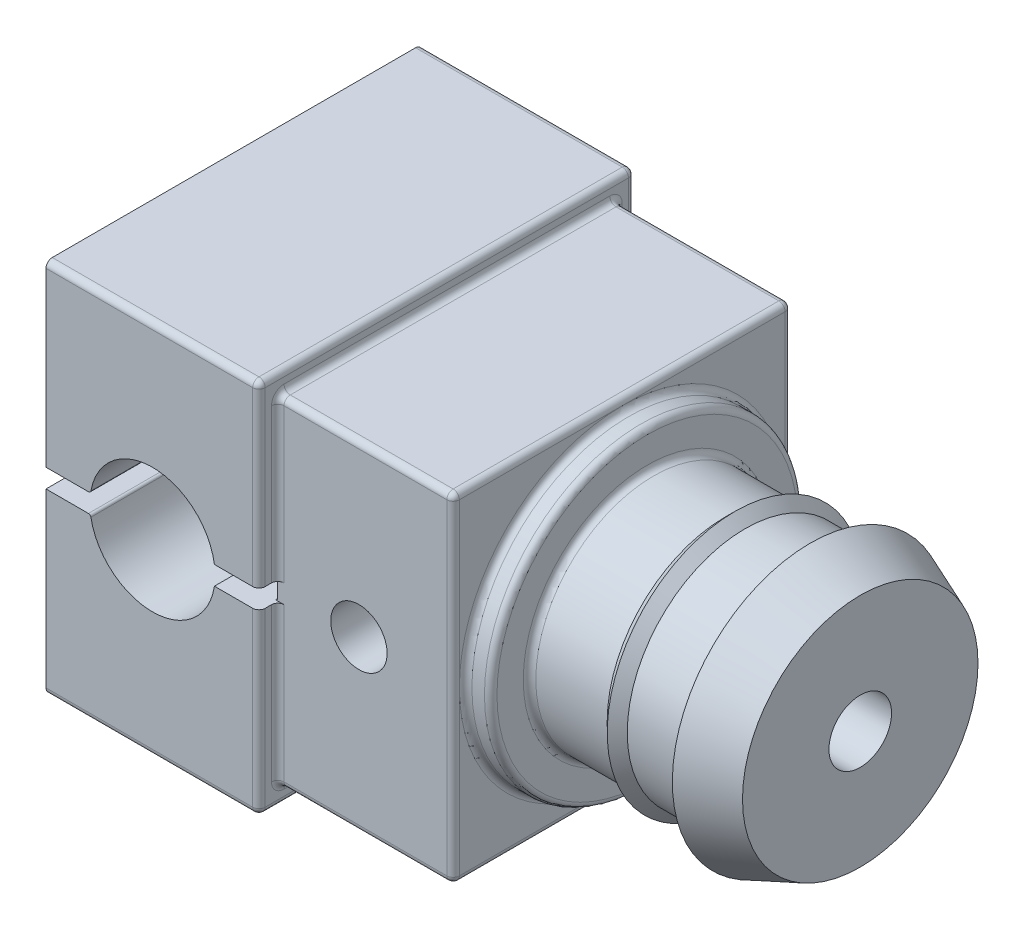
SolidWorks part; units mm, degrees
ref_plane "Front Plane" through (0, 0, 0) normal (0, 0, 1) x (1, 0, 0)
ref_plane "Top Plane" through (0, 0, 0) normal (0, 1, 0) x (1, 0, 0)
ref_plane "Right Plane" through (0, 0, 0) normal (1, 0, 0) x (0, 0, -1)
sketch "Sketch4" plane through (0, 0, 0) normal (0, 0, 1) x (1, 0, 0)
  line L0 (0, 0) -> (0, 9.4)
  line L1 (17, 9.4) -> (17, 0)
  line L2 (17, 0) -> (0, 0)
  line L3 (17, 9.4) -> (13, 11)
  line L4 (13, 11) -> (13, 9.4)
  line L5 (0, 9.4) -> (6.2, 9.4)
  line L6 (7.8, 9.4) -> (7, 10.2)
  line L7 (7, 10.2) -> (6.2, 9.4)
  line L8 (7.8, 9.4) -> (13, 9.4)
  line L9 (7, 10.2) -> (7, 9.4) construction
  line L10 (7.8, 9.4) -> (7, 9.4) construction
  point P9 (7, 9.4)
  dimension "D1" = 13
  dimension "D2" = 9.4
  dimension "D3" = 1.6
  dimension "D4" = 4
  dimension "D5" = 10
  dimension "D6" = 0.8
revolve "Revolve2" add sketch "Sketch4" angle 360 about L2
sketch "Sketch5" plane through (0, 0, 0) normal (-1, 0, 0) x (0, 0, 1)
  circle A0 centre (0, 0) radius 12.5
extrude "Boss-Extrude1" add sketch "Sketch5" along normal blind 2
sketch "Sketch6" plane through (-2, 0, 0) normal (-1, 0, 0) x (0, 0, 1)
  line L1 (-13.5, 13.5) -> (13.5, 13.5)
  line L2 (-13.5, 13.5) -> (-13.5, -13.5)
  line L3 (-13.5, -13.5) -> (13.5, -13.5)
  line L4 (13.5, 13.5) -> (13.5, -13.5)
  line L5 (-13.5, 13.5) -> (13.5, -13.5) construction
  line L6 (-13.5, -13.5) -> (13.5, 13.5) construction
  point P0 (0, 0)
  dimension "D1" = 27
  dimension "D2" = 27
extrude "Boss-Extrude2" add sketch "Sketch6" along normal blind 14
sketch "Sketch8" plane through (-16, 0, 0) normal (-1, 0, 0) x (0, 0, 1)
  line L1 (-15, -15) -> (15, -15)
  line L2 (-15, -15) -> (-15, 15)
  line L3 (-15, 15) -> (15, 15)
  line L4 (15, -15) -> (15, 15)
  line L5 (-15, -15) -> (15, 15) construction
  line L6 (-15, 15) -> (15, -15) construction
  point P0 (0, 0)
  dimension "D1" = 30
  dimension "D2" = 30
extrude "Boss-Extrude3" add sketch "Sketch8" along normal blind 17
sketch "Sketch9" plane through (0, 0, 13.5) normal (0, 0, 1) x (1, 0, 0)
  circle A0 centre (-9.5196, 0) radius 2.25
extrude "Cut-Extrude1" cut sketch "Sketch9" against normal blind 16
sketch "Sketch10" plane through (17, 0, 0) normal (1, 0, 0) x (0, 0, -1)
  circle A0 centre (0, 0) radius 2.5
extrude "Cut-Extrude2" cut sketch "Sketch10" against normal blind 26
sketch "Sketch11" plane through (0, 0, 15) normal (0, 0, 1) x (1, 0, 0)
  line L0 (-24.5, 15) -> (-24.5, -15) construction
  line L1 (-33, 15) -> (-16, 15) construction
  line L2 (-33, -15) -> (-16, -15) construction
  line L3 (-16, 0) -> (-33, 0) construction
  line L4 (-16, -15) -> (-16, 15) construction
  line L5 (-33, -15) -> (-33, 15) construction
  line L6 (-20.4692, 0.75) -> (-16, 0.75)
  line L7 (-16, 0.75) -> (-16, -0.75)
  line L8 (-16, -13.5) -> (-16, 13.5) construction
  line L9 (-16, -0.75) -> (-20.4692, -0.75)
  line L10 (-28.5308, 0.75) -> (-35.5028, 0.75)
  line L11 (-35.5028, 0.75) -> (-35.5028, -0.75)
  line L12 (-35.5028, -0.75) -> (-28.5308, -0.75)
  arc A0 (-20.4692, 0.75) -> (-28.5308, 0.75) centre (-24.5, 0) ccw
  arc A1 (-28.5308, -0.75) -> (-20.4692, -0.75) centre (-24.5, 0) ccw
  dimension "D1" = 0.75
  dimension "D5" = 4.1
  dimension "D2" = 0.75
  dimension "D3" = 0.75
  dimension "D4" = 0.75
extrude "Cut-Extrude3" cut sketch "Sketch11" against normal blind 24
sketch "Sketch12" plane through (-33, 0, 0) normal (-1, 0, 0) x (0, 0, 1)
  line L0 (0, -1.5122) -> (-8, -1.5122)
  line L1 (0, -16.5) -> (0, 16.5) construction
  dimension "D1" = 8
sketch "Sketch15" plane through (0, 0, 15) normal (0, 0, 1) x (1, 0, 0)
  circle A0 centre (-24.5, 0) radius 5
  dimension "D1" = 10
extrude "Cut-Extrude4" cut sketch "Sketch15" against normal blind 8 contours A0
fillet "Fillet3" radius 0.5 20 edges at (-16, 0, -13.5) (-16, 13.5, 0) (-9, 13.5, 13.5) (-16, 7.125, 13.5) (-16, 7.875, 15) (-16, -7.875, 15) (-16, -7.125, 13.5) (-16, -15, 0) (-16, -13.5, 0) (-9, -13.5, 13.5) (-9, -13.5, -13.5) (-9, 13.5, -13.5) (-2, 13.5, 0) (-2, 0, 13.5) (-2, -13.5, 0) (-2, 0, -13.5) (-2, 0, 12.5) (-16, 0, -15) (0, 0, 12.5) (0, 9.4, 0)
fillet "Fillet4" radius 0.5 9 edges at (-16.1464, -14.8536, -14.8536) (-16.1464, -14.8536, 14.8536) (-16.1464, 15, -14.8536) (-16, 15, 0) (-16.1464, 15, 14.8536) (-24.75, 15, -15) (-24.75, -15, -15) (-24.75, -15, 15) (-24.75, 15, 15)
fillet "Fillet6" radius 0.2 13 edges at (-28.9871, -0.75, 7) (-28.9871, 0.75, 7) (-24.5, 4.1, -9) (-30.7654, -0.75, -9) (-30.7654, 0.75, -9) (-29.4434, -0.75, 11) (-29.4434, 0.75, 11) (-24.5, -4.1, 7) (-24.5, -5, 7) (-24.5, 4.1, 7) (-24.5, 5, 7) (-16, -0.75, 2.25) (-16, 0.75, 2.25)
